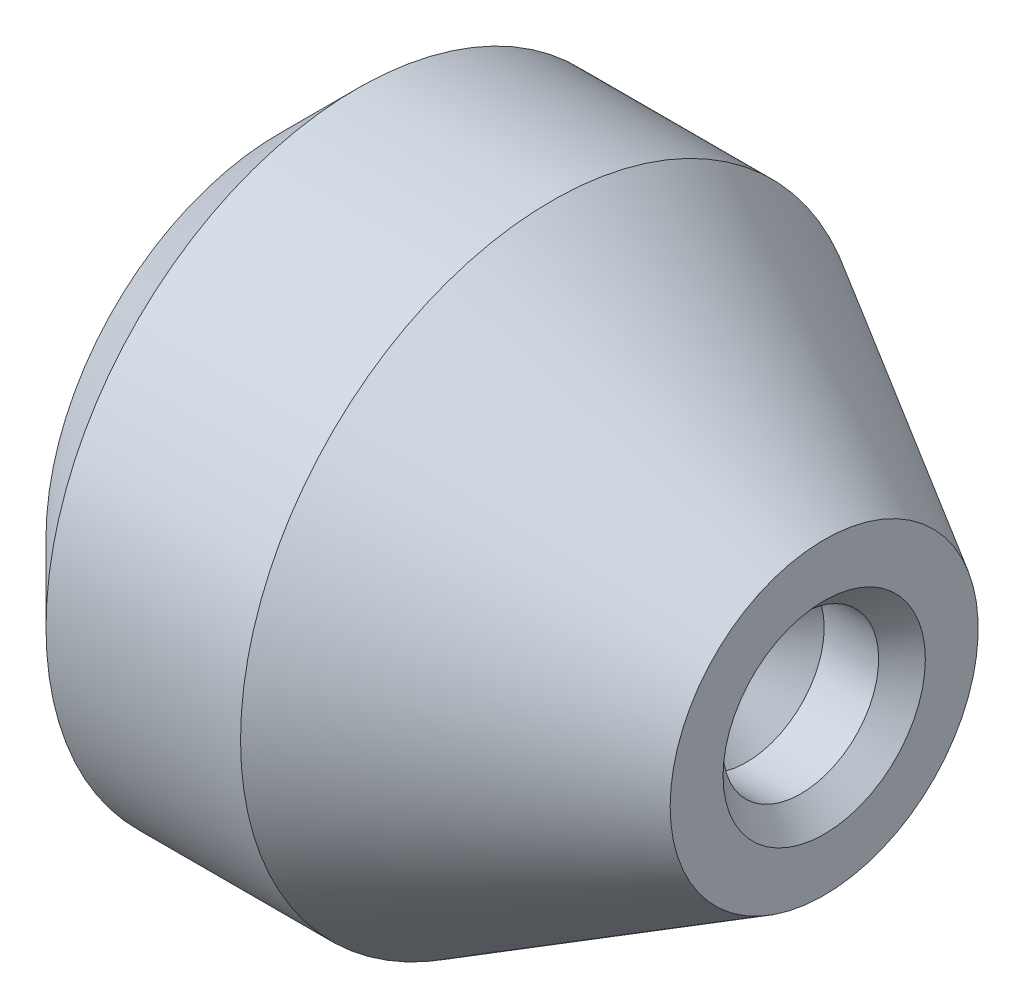
SolidWorks part; units mm, degrees
material "7075-T6 (SN)"
ref_plane "Front Plane" through (0, 0, 0) normal (0, 0, 1) x (1, 0, 0)
ref_plane "Top Plane" through (0, 0, 0) normal (0, 1, 0) x (1, 0, 0)
ref_plane "Right Plane" through (0, 0, 0) normal (1, 0, 0) x (0, 0, -1)
sketch "Sketch1" plane through (0, 0, 0) normal (0, 1, 0) x (1, 0, 0)
  line L0 (-1.0851, 0) -> (2.0426, 0) construction
  line L1 (0, 0) -> (0, 2.5)
  line L2 (0, 2.5) -> (-3, 2.5)
  line L3 (-3, 2.5) -> (-3, 3)
  line L4 (-3, 3) -> (-2, 4)
  line L5 (-2, 4) -> (0.5, 4)
  line L6 (0.5, 4) -> (4, 1.9793)
  line L7 (4, 1.9793) -> (4, 0)
  line L8 (0, 0) -> (4, 0)
  dimension "D1" = 2.5
  dimension "D2" = 3
  dimension "D3" = 7
  dimension "D4" = 3.5
  dimension "D5" = 30
  dimension "D6" = 1
  dimension "D7" = 1
  dimension "D8" = 4
revolve "Revolve1" add sketch "Sketch1" angle 360 about L0
sketch "Sketch2" plane through (4, 0, 0) normal (1, 0, 0) x (0, 0, -1)
  circle A0 centre (0, 0) radius 1
  dimension "D1" = 2
extrude "Cut-Extrude1" cut sketch "Sketch2" against normal blind 0.3
chamfer "Chamfer1" distance 0.3 angle 45 1 edges at (4, 0, -1)
sketch "Sketch3" plane through (3.7, 0, 0) normal (1, 0, 0) x (0, 0, -1)
  circle A1 centre (0, 0) radius 1
  circle A2 centre (0, 0) radius 1
  dimension "D1" = 0
extrude "Cut-Extrude2" cut sketch "Sketch3" against normal blind 0.7
sketch "Sketch4" plane through (3, 0, 0) normal (1, 0, 0) x (0, 0, -1)
  circle A1 centre (0, 0) radius 1
  circle A2 centre (0, 0) radius 1
  dimension "D1" = 0
extrude "Cut-Extrude3" cut sketch "Sketch4" against normal blind 1 draft 45
